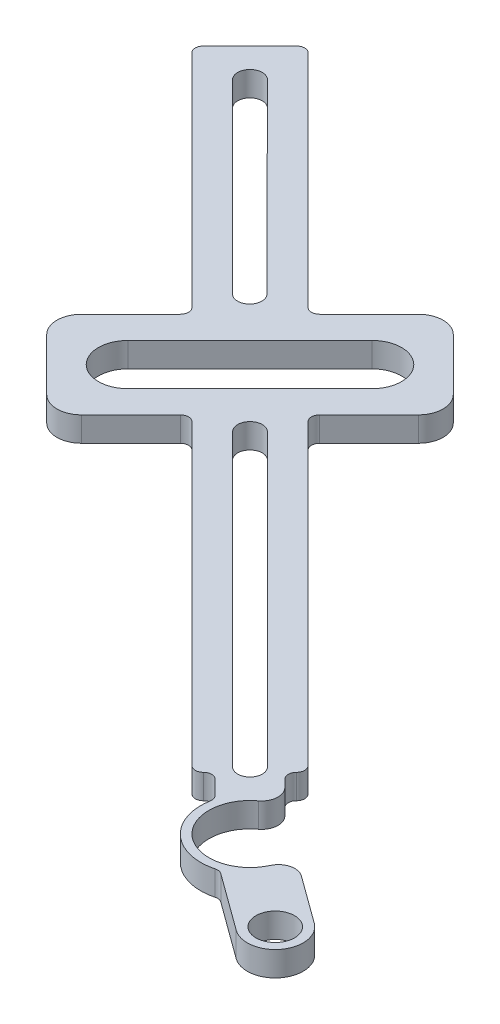
SolidWorks part; units mm, degrees
ref_plane "Front Plane" through (0, 0, 0) normal (0, 0, 1) x (1, 0, 0)
ref_plane "Top Plane" through (0, 0, 0) normal (0, 1, 0) x (1, 0, 0)
ref_plane "Right Plane" through (0, 0, 0) normal (1, 0, 0) x (0, 0, -1)
sketch "Sketch1" plane through (0, 0, 0) normal (0, 1, 0) x (1, 0, 0)
  line L0 (137.4646, -95.9422) -> (102.825, -61.3026) construction
  line L1 (137.4646, -95.9422) -> (148.7808, -104.1849) construction
  line L4 (150.7826, -101.4366) -> (142.4296, -95.3524)
  line L5 (139.4588, -101.6011) -> (146.779, -106.9331)
  line L6 (120.033, -82.7533) -> (124.2757, -78.5107) construction
  line L8 (77.9969, -51.3237) -> (92.8461, -36.4745)
  line L9 (127.4264, -92.9751) -> (128.8406, -91.5608)
  line L10 (128.8406, -91.5608) -> (131.669, -94.3893)
  line L11 (97.513, -47.5054) -> (103.5234, -41.495)
  line L12 (103.5234, -37.2523) -> (97.1595, -30.8884)
  line L13 (92.9168, -30.8884) -> (86.9064, -36.8988)
  line L14 (85.4922, -36.8988) -> (58.6221, -10.0287)
  line L15 (57.2079, -10.0287) -> (51.5511, -15.6856)
  line L16 (51.5511, -17.0998) -> (78.4211, -43.9698)
  line L17 (78.4211, -45.3841) -> (72.4107, -51.3945)
  line L18 (72.4107, -55.6371) -> (78.7747, -62.0011)
  line L19 (83.0173, -62.0011) -> (89.0277, -55.9907)
  line L20 (90.442, -55.9907) -> (133.929, -99.4777)
  line L21 (141.0001, -92.4067) -> (97.513, -48.9196)
  line L22 (97.513, -47.5054) -> (103.5234, -41.495)
  line L23 (103.5234, -37.2523) -> (97.1595, -30.8884)
  line L24 (92.9168, -30.8884) -> (86.9064, -36.8988)
  line L25 (85.4922, -36.8988) -> (58.6221, -10.0287)
  line L26 (57.2079, -10.0287) -> (51.5511, -15.6856)
  line L27 (51.5511, -17.0998) -> (78.4211, -43.9698)
  line L28 (78.4211, -45.3841) -> (72.4107, -51.3945)
  line L29 (72.4107, -55.6371) -> (78.7747, -62.0011)
  line L30 (83.0173, -62.0011) -> (89.0277, -55.9907)
  line L31 (90.442, -55.9907) -> (127.4264, -92.9751)
  line L32 (134.4974, -85.904) -> (97.513, -48.9196)
  line L33 (134.4974, -85.904) -> (133.0832, -87.3182)
  line L34 (133.0832, -87.3182) -> (136.7574, -90.9924)
  line L35 (83.088, -56.4149) -> (97.9373, -41.5657)
  line L37 (94.4017, -52.9132) -> (79.5525, -38.064) construction
  line L38 (79.4787, -40.0838) -> (81.5723, -37.9902) construction
  line L39 (96.0988, -52.4551) -> (131.4541, -87.8105)
  line L40 (129.3328, -89.9318) -> (93.9775, -54.5764)
  line L41 (58.9757, -15.332) -> (81.5723, -37.9902)
  line L42 (79.4787, -40.0838) -> (56.8544, -17.4533)
  circle A0 centre (148.7808, -104.1849) radius 2.35
  arc A1 (142.4296, -95.3524) -> (136.7574, -90.9924) centre (137.4646, -95.9422) cw
  arc A2 (77.9969, -51.3237) -> (83.088, -56.4149) centre (80.5425, -53.8693) ccw
  arc A4 (146.779, -106.9331) -> (150.7826, -101.4366) centre (148.7808, -104.1849) ccw
  arc A6 (139.4588, -101.6011) -> (131.669, -94.3893) centre (137.4646, -95.9422) cw
  arc A7 (92.8461, -36.4745) -> (97.9373, -41.5657) centre (95.3917, -39.0201) cw
  arc A8 (129.3328, -89.9318) -> (131.4541, -87.8105) centre (130.3935, -88.8711) ccw construction
  arc A9 (96.3816, -40.01) -> (94.4017, -38.0301) centre (95.3917, -39.0201) ccw construction
  arc A10 (96.3816, -40.01) -> (94.4017, -38.0301) centre (95.3917, -39.0201) ccw construction
  arc A11 (97.513, -47.5054) -> (97.513, -48.9196) centre (98.2201, -48.2125) ccw
  arc A12 (103.5234, -41.495) -> (103.5234, -37.2523) centre (101.4021, -39.3736) ccw
  arc A13 (97.1595, -30.8884) -> (92.9168, -30.8884) centre (95.0381, -33.0097) ccw
  arc A14 (85.4922, -36.8988) -> (86.9064, -36.8988) centre (86.1993, -36.1917) ccw
  arc A15 (58.6221, -10.0287) -> (57.2079, -10.0287) centre (57.915, -10.7358) ccw
  arc A16 (51.5511, -15.6856) -> (51.5511, -17.0998) centre (52.2582, -16.3927) ccw
  arc A17 (78.4211, -45.3841) -> (78.4211, -43.9698) centre (77.714, -44.6769) ccw
  arc A18 (72.4107, -51.3945) -> (72.4107, -55.6371) centre (74.532, -53.5158) ccw
  arc A19 (78.7747, -62.0011) -> (83.0173, -62.0011) centre (80.896, -59.8797) ccw
  arc A20 (90.442, -55.9907) -> (89.0277, -55.9907) centre (89.7348, -56.6978) ccw
  arc A21 (133.929, -99.4777) -> (141.0001, -92.4067) centre (137.4646, -95.9422) ccw
  arc A22 (97.513, -47.5054) -> (97.513, -48.9196) centre (98.2201, -48.2125) ccw
  arc A23 (103.5234, -41.495) -> (103.5234, -37.2523) centre (101.4021, -39.3736) ccw
  arc A24 (97.1595, -30.8884) -> (92.9168, -30.8884) centre (95.0381, -33.0097) ccw
  arc A25 (85.4922, -36.8988) -> (86.9064, -36.8988) centre (86.1993, -36.1917) ccw
  arc A26 (58.6221, -10.0287) -> (57.2079, -10.0287) centre (57.915, -10.7358) ccw
  arc A27 (51.5511, -15.6856) -> (51.5511, -17.0998) centre (52.2582, -16.3927) ccw
  arc A28 (78.4211, -45.3841) -> (78.4211, -43.9698) centre (77.714, -44.6769) ccw
  arc A29 (72.4107, -51.3945) -> (72.4107, -55.6371) centre (74.532, -53.5158) ccw
  arc A30 (78.7747, -62.0011) -> (83.0173, -62.0011) centre (80.896, -59.8797) ccw
  arc A31 (90.442, -55.9907) -> (89.0277, -55.9907) centre (89.7348, -56.6978) ccw
  arc A32 (79.5525, -52.8794) -> (81.5324, -54.8593) centre (80.5425, -53.8693) ccw construction
  arc A33 (79.5525, -52.8794) -> (81.5324, -54.8593) centre (80.5425, -53.8693) ccw construction
  arc A36 (58.9757, -15.332) -> (56.8544, -17.4533) centre (57.915, -16.3927) ccw construction
  arc A37 (129.3328, -89.9318) -> (131.4541, -87.8105) centre (130.3935, -88.8711) ccw
  arc A38 (96.0988, -52.4551) -> (93.9775, -54.5764) centre (95.0381, -53.5158) ccw
  arc A39 (79.4787, -40.0838) -> (81.5723, -37.9902) centre (80.5255, -39.037) ccw
  arc A40 (58.9757, -15.332) -> (56.8544, -17.4533) centre (57.915, -16.3927) ccw
  point P38 (122.1544, -80.632)
  dimension "D3" = 4.7
  dimension "D4" = 6
  dimension "D5" = 5
  dimension "D2" = 3.4
  dimension "D7" = 3.6
  dimension "D8" = 32
  dimension "D12" = 1.5
  dimension "D6" = 6
  dimension "D9" = 32
  dimension "D10" = 50
  dimension "D11" = 50
  dimension "D13" = 2
  dimension "D14" = 4
  dimension "D1" = 0
extrude "Boss-Extrude1" add sketch "Sketch1" along normal blind 3
fillet "Fillet1" radius 1 6 edges at (139.4588, 1.5, 101.6011) (131.669, 1.5, 94.3893) (133.0832, 1.5, 87.3182) (134.4974, 1.5, 85.904) (128.8406, 1.5, 91.5608) (127.4264, 1.5, 92.9751)
fillet "Fillet2" radius 2 2 edges at (142.4296, 1.5, 95.3524) (136.7574, 1.5, 90.9924)
sketch "Sketch2" plane through (0, 3, 0) normal (0, 1, 0) x (1, 0, 0)
  line L2 (81.5723, -37.9902) -> (58.9757, -15.332)
  line L3 (56.8544, -17.4533) -> (79.4787, -40.0838)
  line L4 (81.5723, -37.9902) -> (58.9757, -15.332)
  line L5 (56.8544, -17.4533) -> (79.4787, -40.0838)
  line L6 (131.4541, -87.8105) -> (96.0988, -52.4551)
  line L7 (93.9775, -54.5764) -> (129.3328, -89.9318)
  line L8 (131.4541, -87.8105) -> (96.0988, -52.4551)
  line L9 (93.9775, -54.5764) -> (129.3328, -89.9318)
  line L10 (83.088, -56.4149) -> (97.9373, -41.5657)
  line L11 (92.8461, -36.4745) -> (77.9969, -51.3237)
  line L12 (83.088, -56.4149) -> (97.9373, -41.5657)
  line L13 (92.8461, -36.4745) -> (77.9969, -51.3237)
  line L27 (150.7826, -101.4366) -> (145.0102, -97.232)
  line L28 (134.6869, -88.9219) -> (133.7903, -88.0253)
  line L29 (133.7903, -85.1969) -> (97.513, -48.9196)
  line L30 (97.513, -47.5054) -> (103.5234, -41.495)
  line L31 (103.5234, -37.2523) -> (97.1595, -30.8884)
  line L32 (92.9168, -30.8884) -> (86.9064, -36.8988)
  line L33 (85.4922, -36.8988) -> (58.6221, -10.0287)
  line L34 (57.2079, -10.0287) -> (51.5511, -15.6856)
  line L35 (51.5511, -17.0998) -> (78.4211, -43.9698)
  line L36 (78.4211, -45.3841) -> (72.4107, -51.3945)
  line L37 (72.4107, -55.6371) -> (78.7747, -62.0011)
  line L38 (83.0173, -62.0011) -> (89.0277, -55.9907)
  line L39 (90.442, -55.9907) -> (126.7192, -92.268)
  line L40 (129.5477, -92.268) -> (131.2812, -94.0015)
  line L41 (139.8634, -101.8958) -> (146.779, -106.9331)
  line L42 (150.7826, -101.4366) -> (145.0102, -97.232)
  line L43 (134.6869, -88.9219) -> (133.7903, -88.0253)
  line L44 (133.7903, -85.1969) -> (97.513, -48.9196)
  line L45 (97.513, -47.5054) -> (103.5234, -41.495)
  line L46 (103.5234, -37.2523) -> (97.1595, -30.8884)
  line L47 (92.9168, -30.8884) -> (86.9064, -36.8988)
  line L48 (85.4922, -36.8988) -> (58.6221, -10.0287)
  line L49 (57.2079, -10.0287) -> (51.5511, -15.6856)
  line L50 (51.5511, -17.0998) -> (78.4211, -43.9698)
  line L51 (78.4211, -45.3841) -> (72.4107, -51.3945)
  line L52 (72.4107, -55.6371) -> (78.7747, -62.0011)
  line L53 (83.0173, -62.0011) -> (89.0277, -55.9907)
  line L54 (90.442, -55.9907) -> (126.7192, -92.268)
  line L55 (129.5477, -92.268) -> (131.2812, -94.0015)
  line L56 (139.8634, -101.8958) -> (146.779, -106.9331)
  circle A1 centre (148.7808, -104.1849) radius 2.35
  arc A2 (79.4787, -40.0838) -> (81.5723, -37.9902) centre (80.5255, -39.037) ccw
  arc A3 (58.9757, -15.332) -> (56.8544, -17.4533) centre (57.915, -16.3927) ccw
  arc A4 (79.4787, -40.0838) -> (81.5723, -37.9902) centre (80.5255, -39.037) ccw
  arc A5 (58.9757, -15.332) -> (56.8544, -17.4533) centre (57.915, -16.3927) ccw
  arc A6 (129.3328, -89.9318) -> (131.4541, -87.8105) centre (130.3935, -88.8711) ccw
  arc A7 (96.0988, -52.4551) -> (93.9775, -54.5764) centre (95.0381, -53.5158) ccw
  arc A8 (129.3328, -89.9318) -> (131.4541, -87.8105) centre (130.3935, -88.8711) ccw
  arc A9 (96.0988, -52.4551) -> (93.9775, -54.5764) centre (95.0381, -53.5158) ccw
  arc A10 (77.9969, -51.3237) -> (83.088, -56.4149) centre (80.5425, -53.8693) ccw
  arc A11 (97.9373, -41.5657) -> (92.8461, -36.4745) centre (95.3917, -39.0201) ccw
  arc A12 (77.9969, -51.3237) -> (83.088, -56.4149) centre (80.5425, -53.8693) ccw
  arc A13 (97.9373, -41.5657) -> (92.8461, -36.4745) centre (95.3917, -39.0201) ccw
  circle A14 centre (148.7808, -104.1849) radius 2.35
  arc A35 (145.0102, -97.232) -> (142.0132, -98.0182) centre (143.8326, -98.8486) ccw
  arc A36 (134.4704, -91.9378) -> (142.0132, -98.0182) centre (137.4646, -95.9422) ccw
  arc A37 (134.4704, -91.9378) -> (134.6869, -88.9219) centre (133.2727, -90.3361) ccw
  arc A38 (133.7903, -86.6111) -> (133.7903, -88.0253) centre (134.4974, -87.3182) ccw
  arc A39 (133.7903, -86.6111) -> (133.7903, -85.1969) centre (133.0832, -85.904) ccw
  arc A40 (97.513, -47.5054) -> (97.513, -48.9196) centre (98.2201, -48.2125) ccw
  arc A41 (103.5234, -41.495) -> (103.5234, -37.2523) centre (101.4021, -39.3736) ccw
  arc A42 (97.1595, -30.8884) -> (92.9168, -30.8884) centre (95.0381, -33.0097) ccw
  arc A43 (85.4922, -36.8988) -> (86.9064, -36.8988) centre (86.1993, -36.1917) ccw
  arc A44 (58.6221, -10.0287) -> (57.2079, -10.0287) centre (57.915, -10.7358) ccw
  arc A45 (51.5511, -15.6856) -> (51.5511, -17.0998) centre (52.2582, -16.3927) ccw
  arc A46 (78.4211, -45.3841) -> (78.4211, -43.9698) centre (77.714, -44.6769) ccw
  arc A47 (72.4107, -51.3945) -> (72.4107, -55.6371) centre (74.532, -53.5158) ccw
  arc A48 (78.7747, -62.0011) -> (83.0173, -62.0011) centre (80.896, -59.8797) ccw
  arc A49 (90.442, -55.9907) -> (89.0277, -55.9907) centre (89.7348, -56.6978) ccw
  arc A50 (126.7192, -92.268) -> (128.1335, -92.268) centre (127.4264, -91.5608) ccw
  arc A51 (129.5477, -92.268) -> (128.1335, -92.268) centre (128.8406, -92.9751) ccw
  arc A52 (131.5585, -94.8848) -> (131.2812, -94.0015) centre (130.5741, -94.7086) ccw
  arc A53 (131.5585, -94.8848) -> (139.016, -101.7381) centre (137.4646, -95.9422) ccw
  arc A54 (139.8634, -101.8958) -> (139.016, -101.7381) centre (139.2746, -102.7041) ccw
  arc A55 (146.779, -106.9331) -> (150.7826, -101.4366) centre (148.7808, -104.1849) ccw
  arc A56 (145.0102, -97.232) -> (142.0132, -98.0182) centre (143.8326, -98.8486) ccw
  arc A57 (134.4704, -91.9378) -> (142.0132, -98.0182) centre (137.4646, -95.9422) ccw
  arc A58 (134.4704, -91.9378) -> (134.6869, -88.9219) centre (133.2727, -90.3361) ccw
  arc A59 (133.7903, -86.6111) -> (133.7903, -88.0253) centre (134.4974, -87.3182) ccw
  arc A60 (133.7903, -86.6111) -> (133.7903, -85.1969) centre (133.0832, -85.904) ccw
  arc A61 (97.513, -47.5054) -> (97.513, -48.9196) centre (98.2201, -48.2125) ccw
  arc A62 (103.5234, -41.495) -> (103.5234, -37.2523) centre (101.4021, -39.3736) ccw
  arc A63 (97.1595, -30.8884) -> (92.9168, -30.8884) centre (95.0381, -33.0097) ccw
  arc A64 (85.4922, -36.8988) -> (86.9064, -36.8988) centre (86.1993, -36.1917) ccw
  arc A65 (58.6221, -10.0287) -> (57.2079, -10.0287) centre (57.915, -10.7358) ccw
  arc A66 (51.5511, -15.6856) -> (51.5511, -17.0998) centre (52.2582, -16.3927) ccw
  arc A67 (78.4211, -45.3841) -> (78.4211, -43.9698) centre (77.714, -44.6769) ccw
  arc A68 (72.4107, -51.3945) -> (72.4107, -55.6371) centre (74.532, -53.5158) ccw
  arc A69 (78.7747, -62.0011) -> (83.0173, -62.0011) centre (80.896, -59.8797) ccw
  arc A70 (90.442, -55.9907) -> (89.0277, -55.9907) centre (89.7348, -56.6978) ccw
  arc A71 (126.7192, -92.268) -> (128.1335, -92.268) centre (127.4264, -91.5608) ccw
  arc A72 (129.5477, -92.268) -> (128.1335, -92.268) centre (128.8406, -92.9751) ccw
  arc A73 (131.5585, -94.8848) -> (131.2812, -94.0015) centre (130.5741, -94.7086) ccw
  arc A74 (131.5585, -94.8848) -> (139.016, -101.7381) centre (137.4646, -95.9422) ccw
  arc A75 (139.8634, -101.8958) -> (139.016, -101.7381) centre (139.2746, -102.7041) ccw
  arc A76 (146.779, -106.9331) -> (150.7826, -101.4366) centre (148.7808, -104.1849) ccw
  dimension "D1" = 0
  dimension "D2" = 0
  dimension "D3" = 0
  dimension "D4" = 0
  dimension "D5" = 0
